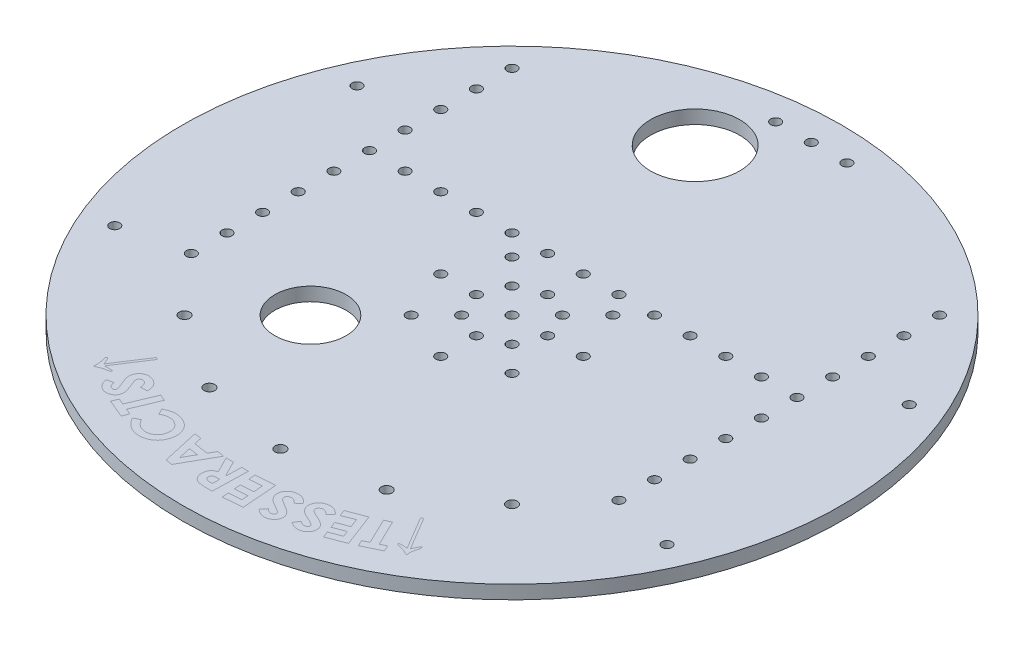
SolidWorks part; units mm, degrees
material "Balsa"
ref_plane "Front Plane" through (0, 0, 0) normal (0, 0, 1) x (1, 0, 0)
ref_plane "Top Plane" through (0, 0, 0) normal (0, 1, 0) x (1, 0, 0)
ref_plane "Right Plane" through (0, 0, 0) normal (1, 0, 0) x (0, 0, -1)
sketch "Sketch1" plane through (0, 0, 0) normal (0, 1, 0) x (1, 0, 0)
  circle A0 centre (0, 0) radius 117.475
  dimension "D1" = 234.95
extrude "Boss-Extrude1" add sketch "Sketch1" against normal blind 4.826
sketch "Sketch3" plane through (0, 0, 0) normal (0, 1, 0) x (1, 0, 0)
  line L1 (-114.4075, 26.67) -> (-88.9, 26.67)
  line L2 (0, -92.075) -> (0, -117.475)
  line L3 (-88.9, -26.67) -> (-88.9, 26.67)
  line L4 (0, 0) -> (-88.9, 0) construction
  line L5 (0, 0) -> (0, -117.475) construction
  line L6 (0, 0) -> (0, 117.475) construction
  line L8 (-88.9, -26.67) -> (-114.4075, -26.67)
  line L10 (-84.6624, -36.195) -> (-111.76, -36.195)
  arc A0 (-114.4075, 26.67) -> (-114.4075, -26.67) centre (0, 0) ccw
  circle A1 centre (0, 0) radius 117.475 construction
  arc A3 (-84.6624, -36.195) -> (0, -92.075) centre (0, 0) ccw
  arc A4 (-111.76, -36.195) -> (0, -117.475) centre (0, 0) ccw
  dimension "D1" = 88.9
  dimension "D2" = 53.34
  dimension "D4" = 9.525
  dimension "D5" = 25.4
extrude "Cut-Extrude4" [suppressed] cut sketch "Sketch3" against normal through all
fillet "Fillet1" [suppressed] radius 2.54
mirror "Mirror1" [suppressed] about plane through (0, 0, 0) normal (1, 0, 0)
sketch "Sketch4" plane through (0, 0, 0) normal (0, 1, 0) x (1, 0, 0)
  line L0 (-76.2, 38.1) -> (-76.2, 25.4) construction
  line L1 (-76.2, 25.4) -> (-76.2, 12.7) construction
  line L2 (-76.2, 12.7) -> (-76.2, 0) construction
  line L3 (-76.2, 0) -> (-76.2, -12.7) construction
  line L4 (-76.2, -12.7) -> (-76.2, -25.4) construction
  line L5 (-76.2, -25.4) -> (-76.2, -38.1) construction
  line L6 (0, 0) -> (-76.2, 0) construction
  line L12 (-76.2, 76.2) -> (-76.2, 63.5) construction
  line L13 (-76.2, 63.5) -> (-76.2, 50.8) construction
  line L14 (-76.2, 50.8) -> (-76.2, 38.1) construction
  circle A0 centre (-76.2, 0) radius 1.778
  circle A1 centre (-76.2, 12.7) radius 1.778
  circle A2 centre (-76.2, 25.4) radius 1.778
  circle A3 centre (-76.2, 38.1) radius 1.778
  circle A4 centre (-76.2, -12.7) radius 1.778
  circle A5 centre (-76.2, -25.4) radius 1.778
  circle A6 centre (-76.2, -38.1) radius 1.778
  circle A7 centre (-76.2, 50.8) radius 1.778
  circle A8 centre (-76.2, 63.5) radius 1.778
  circle A9 centre (-76.2, 76.2) radius 1.778
  dimension "D2" = 3.556
  dimension "D1" = 12.7
  dimension "D3" = 76.2
extrude "Cut-Extrude5" cut sketch "Sketch4" against normal through all
mirror "Mirror3" about plane through (0, 0, 0) normal (1, 0, 0) of "Cut-Extrude5"
sketch "Sketch5" plane through (0, 0, 0) normal (0, 1, 0) x (1, 0, 0)
  circle A0 centre (0, 0) radius 1.778
  dimension "D1" = 3.556
extrude "Cut-Extrude6" cut sketch "Sketch5" against normal through all
sketch "Sketch6" plane through (0, 0, 0) normal (0, 1, 0) x (1, 0, 0)
  line L0 (0, 0) -> (0, 25.4) construction
  line L1 (0, 25.4) -> (12.7, 25.4) construction
  line L2 (12.7, 25.4) -> (25.4, 25.4) construction
  line L3 (25.4, 25.4) -> (38.1, 25.4) construction
  line L4 (-38.1, 25.4) -> (-50.8, 25.4) construction
  line L5 (38.1, 25.4) -> (50.8, 25.4) construction
  line L6 (0, 25.4) -> (-12.7, 25.4) construction
  line L7 (-12.7, 25.4) -> (-25.4, 25.4) construction
  line L8 (-25.4, 25.4) -> (-38.1, 25.4) construction
  line L9 (-50.8, 25.4) -> (-63.5, 25.4) construction
  line L10 (50.8, 25.4) -> (63.5, 25.4) construction
  line L11 (0, 106.68) -> (12.7, 106.68) construction
  line L12 (12.7, 106.68) -> (25.4, 106.68) construction
  line L13 (25.4, 106.68) -> (38.1, 106.68) construction
  line L14 (-38.1, 106.68) -> (-50.8, 106.68) construction
  line L15 (38.1, 106.68) -> (50.8, 106.68) construction
  line L16 (0, 106.68) -> (-12.7, 106.68) construction
  line L17 (-12.7, 106.68) -> (-25.4, 106.68) construction
  line L18 (-25.4, 106.68) -> (-38.1, 106.68) construction
  line L19 (-50.8, 106.68) -> (-63.5, 106.68) construction
  line L20 (50.8, 106.68) -> (63.5, 106.68) construction
  line L21 (0, 25.4) -> (0, 106.68) construction
  circle A0 centre (0, 25.4) radius 1.778
  circle A1 centre (-12.7, 25.4) radius 1.778
  circle A2 centre (-25.4, 25.4) radius 1.778
  circle A3 centre (-38.1, 25.4) radius 1.778
  circle A4 centre (12.7, 25.4) radius 1.778
  circle A5 centre (25.4, 25.4) radius 1.778
  circle A6 centre (38.1, 25.4) radius 1.778
  circle A7 centre (-50.8, 25.4) radius 1.778
  circle A8 centre (50.8, 25.4) radius 1.778
  circle A9 centre (-63.5, 25.4) radius 1.778
  circle A10 centre (63.5, 25.4) radius 1.778
  circle A11 centre (0, 106.68) radius 1.778
  circle A12 centre (-12.7, 106.68) radius 1.778
  circle A13 centre (-25.4, 106.68) radius 1.778 construction
  circle A14 centre (-38.1, 106.68) radius 1.778 construction
  circle A15 centre (12.7, 106.68) radius 1.778
  circle A16 centre (25.4, 106.68) radius 1.778 construction
  circle A17 centre (38.1, 106.68) radius 1.778 construction
  circle A18 centre (-50.8, 106.68) radius 1.778 construction
  circle A19 centre (50.8, 106.68) radius 1.778 construction
  circle A20 centre (-63.5, 106.68) radius 1.778 construction
  circle A21 centre (63.5, 106.68) radius 1.778 construction
  dimension "D1" = 3.556
  dimension "D4" = 3.556
  dimension "D2" = 12.7
  dimension "D3" = 25.4
  dimension "D5" = 12.7
  dimension "D6" = 81.28
extrude "Cut-Extrude7" cut sketch "Sketch6" against normal through all
sketch "Sketch9" plane through (0, 0, 0) normal (0, 1, 0) x (1, 0, 0)
  line L4 (0, -82.55) -> (0, 0) construction
  circle A1 centre (0, -82.55) radius 1.905
  dimension "D2" = 3.81
  dimension "D1" = 82.55
extrude "Cut-Extrude10" cut sketch "Sketch9" against normal through all
pattern_circular "CirPattern1" count 3 over 45 about axis through (0, -4.826, 0) along (0, 1, 0) of "Cut-Extrude10"
pattern_circular "CirPattern2" count 3 over 45 about axis through (0, -4.826, 0) along (0, 1, 0) of "Cut-Extrude10" reverse direction yes
sketch "Sketch12" plane through (0, 0, 0) normal (0, 1, 0) x (1, 0, 0)
  text T0 "<b>MSE2202B       TRON UWO 2018</b>\r\n<b>TESSERACT COLLECTING ROBOT</b>\r\n<b>ver 2.0.0</b>\r\n<b>JdR CB TW MH</b>" font "Century Gothic" height 5.842
wrap "Wrap1" [suppressed] sketch "Sketch12" source sketch "Sketch12"
sketch "Sketch7" plane through (0, 0, 0) normal (0, 1, 0) x (1, 0, 0)
  line L0 (-8.9803, 8.9803) -> (0, 0) construction
  line L1 (0, 0) -> (8.9803, -8.9803) construction
  line L3 (8.9803, 8.9803) -> (0, 0) construction
  line L4 (0, 0) -> (-8.9803, -8.9803) construction
  line L6 (-12.7, 0) -> (0, 0) construction
  line L7 (0, 0) -> (0, 12.7) construction
  line L9 (12.7, 0) -> (0, 0) construction
  line L10 (0, 0) -> (0, -12.7) construction
  circle A0 centre (0, 12.7) radius 1.778
  circle A1 centre (12.7, 0) radius 1.778
  circle A2 centre (0, -12.7) radius 1.778
  circle A3 centre (-12.7, 0) radius 1.778
  circle A4 centre (-8.9803, 8.9803) radius 1.778
  circle A5 centre (8.9803, 8.9803) radius 1.778
  circle A6 centre (8.9803, -8.9803) radius 1.778
  circle A7 centre (-8.9803, -8.9803) radius 1.778
  dimension "D1" = 45
  dimension "D2" = 3.556
  dimension "D3" = 12.7
extrude "Cut-Extrude8" cut sketch "Sketch7" against normal through all
sketch "Sketch8" plane through (0, 0, 0) normal (0, 1, 0) x (1, 0, 0)
  line L0 (0, 0) -> (-35.921, -35.921) construction
  line L1 (-35.921, -35.921) -> (-35.921, -1.2798) construction
  circle A0 centre (-35.921, -35.921) radius 12.7
  dimension "D3" = 25.4
  dimension "D1" = 45
  dimension "D2" = 50.8
extrude "Cut-Extrude9" cut sketch "Sketch8" against normal through all
sketch "Sketch10" plane through (0, 0, 0) normal (0, 1, 0) x (1, 0, 0)
  line L0 (-19.812, 85.09) -> (-19.812, 0) construction
  line L1 (-19.812, 0) -> (0, 0) construction
  circle A0 centre (-19.812, 85.09) radius 15.875
  dimension "D1" = 31.75
  dimension "D2" = 85.09
  dimension "D3" = 19.812
extrude "Cut-Extrude11" cut sketch "Sketch10" against normal through all
sketch "Sketch14" plane through (0, 0, 0) normal (0, 1, 0) x (1, 0, 0)
  line L0 (0, 0) -> (-55.6246, -77.3206) construction
  line L1 (-55.6246, -77.3206) -> (55.6246, -77.3206) construction
  line L2 (55.6246, -77.3206) -> (0, 0) construction
  arc A0 (-55.6246, -77.3206) -> (55.6246, -77.3206) centre (0, 0) ccw construction
  text T0 "<b>↑TESSERACTS↑</b>" font "Century Gothic" height 12.7
  dimension "D1" = 95.25
wrap "Wrap2" sketch "Sketch14" wrap type scribe source sketch "Sketch14" face at (-19.812, 0, -69.215)
sketch "Sketch15" plane through (0, 0, 0) normal (0, 1, 0) x (1, 0, 0)
  line L0 (0, 0) -> (25.4, 0) construction
  circle A0 centre (25.4, 0) radius 1.778
  circle A1 centre (17.9605, -17.9605) radius 1.778
  circle A2 centre (0, -25.4) radius 1.778
  circle A3 centre (-17.9605, -17.9605) radius 1.778
  circle A4 centre (-25.4, 0) radius 1.778
  circle A5 centre (-17.9605, 17.9605) radius 1.778
  circle A6 centre (0, 25.4) radius 1.778
  circle A7 centre (17.9605, 17.9605) radius 1.778
  point P20 (0, 0)
  dimension "D2" = 3.556
  dimension "D1" = 25.4
  dimension "D3" = 8
extrude "Cut-Extrude12" cut sketch "Sketch15" against normal through all
sketch "Sketch16" plane through (0, 0, 0) normal (0, 1, 0) x (1, 0, 0)
  line L0 (0, 117.475) -> (0, -125.9601) construction
  circle A0 centre (-98.425, 43.18) radius 1.778
  circle A1 centre (-98.425, -43.18) radius 1.778
  circle A2 centre (0, 0) radius 117.475 construction
  circle A3 centre (0, 0) radius 1.778 construction
  circle A4 centre (98.425, -43.18) radius 1.778
  circle A5 centre (98.425, 43.18) radius 1.778
  dimension "D1" = 3.556
  dimension "D2" = 3.556
  dimension "D3" = 98.425
  dimension "D4" = 98.425
  dimension "D5" = 43.18
  dimension "D6" = 43.18
extrude "Cut-Extrude13" cut sketch "Sketch16" against normal through all
